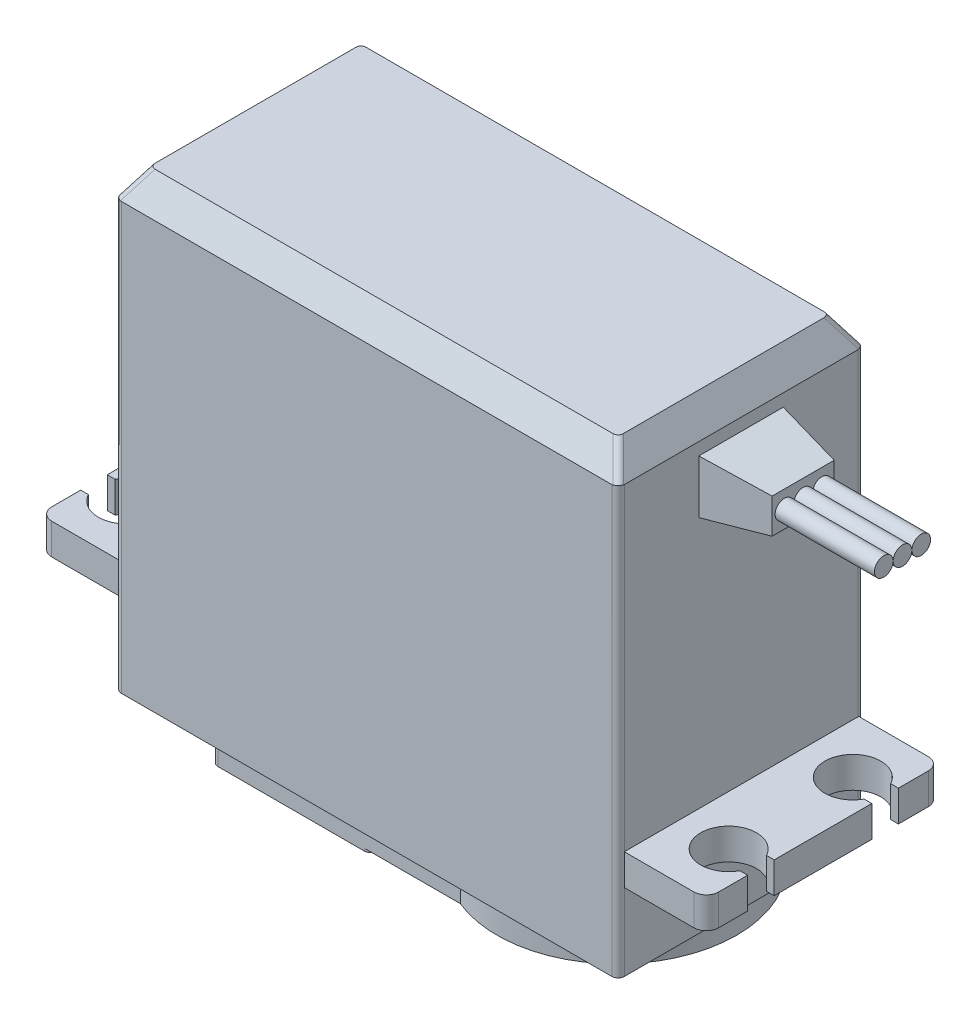
SolidWorks part; units mm, degrees
ref_plane "Front" through (0, 0, 0) normal (0, 0, 1) x (1, 0, 0)
ref_plane "Top" through (0, 0, 0) normal (0, 1, 0) x (1, 0, 0)
ref_plane "Right" through (0, 0, 0) normal (1, 0, 0) x (0, 0, -1)
sketch "Эскиз1" plane through (0, 0, 0) normal (0, 1, 0) x (1, 0, 0)
  line L1 (20.25, -9.9) -> (-20.25, -9.9)
  line L2 (20.25, -9.9) -> (20.25, 9.9)
  line L3 (20.25, 9.9) -> (-20.25, 9.9)
  line L4 (-20.25, -9.9) -> (-20.25, 9.9)
  line L5 (0, 9.9) -> (0, -9.9) construction
  line L6 (20.25, 0) -> (-20.25, 0) construction
  point P0 (0, 0)
  dimension "D1" = 19.8
  dimension "D2" = 40.5
extrude "Body" add sketch "Эскиз1" along normal blind 36.5
chamfer "Фаска1" distance 2.2 distance2 1.4 4 edges at (-20.25, 36.5, 0) (0, 36.5, -9.9) (20.25, 36.5, 0) (0, 36.5, 9.9) first distance on face at (-20.25, 18.25, 0) first distance on face at (0, 18.25, -9.9) first distance on face at (20.25, 18.25, 0) first distance on face at (0, 18.25, 9.9)
fillet "Скругление1" radius 0.5 8 edges at (-20.25, 17.15, -9.9) (-19.55, 35.4, -9.2) (19.55, 35.4, -9.2) (20.25, 17.15, -9.9) (19.55, 35.4, 9.2) (-19.55, 35.4, 9.2) (20.25, 17.15, 9.9) (-20.25, 17.15, 9.9)
ref_plane "Плоскость1" through (0, 6.2, 0) normal (0, -1, 0) x (-1, 0, 0)
sketch "Эскиз2" plane through (0, 6.2, 0) normal (0, -1, 0) x (-1, 0, 0)
  line L1 (-26.85, 9.4728) -> (26.85, 9.4728)
  line L2 (26.85, -9.4) -> (26.85, -6.0698)
  line L3 (-26.85, -9.4) -> (26.85, -9.4)
  line L4 (-26.85, -9.4) -> (-26.85, -6.0698)
  line L5 (0, 9.9) -> (0, -9.9) construction
  line L6 (27.2, 0) -> (-26.85, 0) construction
  line L7 (-24.25, 5) -> (-26.85, 5) construction
  line L8 (-26.2294, 6.0698) -> (-26.85, 6.0698)
  line L9 (-26.2294, 3.9302) -> (-26.85, 3.9302)
  line L10 (-26.85, 6.0698) -> (-26.85, 9.4728)
  line L11 (-26.2294, -3.9302) -> (-26.85, -3.9302)
  line L12 (-26.2294, -6.0698) -> (-26.85, -6.0698)
  line L13 (26.2294, -6.0698) -> (26.85, -6.0698)
  line L14 (26.2294, -3.9302) -> (26.85, -3.9302)
  line L15 (26.2294, 3.9302) -> (26.85, 3.9302)
  line L16 (26.2294, 6.0698) -> (26.85, 6.0698)
  line L17 (26.85, 6.0698) -> (26.85, 9.4728)
  line L18 (26.85, -3.9302) -> (26.85, 3.9302)
  line L19 (-26.85, -3.9302) -> (-26.85, 3.9302)
  line L20 (-20.25, -9.4) -> (-20.25, 9.4) construction
  line L21 (20.25, 9.4) -> (20.25, -9.4) construction
  arc A4 (-26.2294, 3.9302) -> (-26.2294, 6.0698) centre (-24.25, 5) ccw
  arc A5 (-26.2294, -3.9302) -> (-26.2294, -6.0698) centre (-24.25, -5) cw
  arc A6 (26.2294, -3.9302) -> (26.2294, -6.0698) centre (24.25, -5) ccw
  arc A7 (26.2294, 3.9302) -> (26.2294, 6.0698) centre (24.25, 5) cw
  point P0 (0, 0)
  point P5 (-26.85, 0)
  point P38 (-22, 5)
  point P39 (22, 5)
  dimension "D2" = 6.6
  dimension "D4" = 2.25
  dimension "D1" = 53.7
  dimension "D3" = 10
  dimension "D5" = 44
  dimension "D6" = 2.1395
  dimension "D7" = 6.6
extrude "Mount" add sketch "Эскиз2" against normal blind 2.5 contours L15 A7 L16 L17 L1 L10 L8 A4 L9 L4 L11 A5 L12 L3 L2 L13 A6 L14 L18 region at (0, 6.2, -0.039)
fillet "Скругление3" radius 1 4 edges at (-26.85, 7.45, -9.4728) (-26.85, 7.45, 9.4) (26.85, 7.45, -9.4728) (26.85, 7.45, 9.4)
sketch "Эскиз3" plane through (0, 0, 0) normal (0, 0, 1) x (1, 0, 0)
  line L0 (-26.85, 6.2) -> (-20.25, 6.2)
  line L1 (-20.25, 6.2) -> (-20.25, 5.2)
  line L2 (-20.25, 0) -> (-20.25, 6.2) construction
  line L3 (-20.25, 5.2) -> (-26.85, 6.2)
  line L4 (0, 0) -> (0, 36.5) construction
  line L5 (-18.4282, 36.5) -> (18.4282, 36.5) construction
  line L6 (20.25, 5.2) -> (26.85, 6.2)
  line L7 (20.25, 6.2) -> (20.25, 5.2)
  line L8 (26.85, 6.2) -> (20.25, 6.2)
  line L11 (-26.85, 6.2) -> (-26.85, 8.7) construction
  dimension "D1" = 1
extrude "Бобышка-Вытянуть3" add sketch "Эскиз3" along normal mid plane 1
sketch "Эскиз4" plane through (0, 0, 0) normal (0, -1, 0) x (1, 0, 0)
  line L0 (20.25, 9.4) -> (20.25, -9.4) construction
  line L1 (-13.4526, -8.92) -> (-13.4526, -4.6)
  line L2 (-13.4526, -8.92) -> (6.5681, -8.92)
  line L3 (-13.4526, 8.92) -> (6.5681, 8.92)
  line L6 (-13.4526, 4.6) -> (-13.4526, 8.92)
  arc A0 (6.5681, -8.92) -> (6.5681, 8.92) centre (10.25, 0) ccw
  arc A1 (-13.4526, 4.6) -> (-13.4526, -4.6) centre (-11.493, 0) ccw
  point P2 (20.25, 0)
  point P6 (3.35, 0)
  dimension "D1" = 19.3
  dimension "D5" = 5
  dimension "D2" = 10
  dimension "D3" = 17.84
  dimension "D4" = 9.2
extrude "Бобышка-Вытянуть4" add sketch "Эскиз4" along normal blind 2
sketch "Эскиз5" plane through (0, -2, 0) normal (0, -1, 0) x (1, 0, 0)
  line L0 (-13.4526, -8.92) -> (6.5681, -8.92) construction
  line L1 (-13.4526, 8.92) -> (-0.6526, 8.92)
  line L2 (-13.4526, 8.92) -> (-13.4526, -8.92)
  line L3 (-13.4526, -8.92) -> (-0.6526, -8.92)
  line L4 (-0.6526, 8.92) -> (-0.6526, 2)
  line L5 (-0.6526, -2) -> (-0.6526, -8.92)
  line L7 (-1.6526, -7.92) -> (-12.4526, -7.92)
  line L8 (-1.6526, -7.92) -> (-1.6526, 7.92)
  line L9 (-1.6526, 7.92) -> (-12.4526, 7.92)
  line L10 (-12.4526, -7.92) -> (-12.4526, 7.92)
  line L11 (-7.0526, 7.92) -> (-7.0526, -7.92) construction
  line L12 (-1.6526, 0) -> (-12.4526, 0) construction
  arc A0 (-0.6526, 2) -> (-0.6526, -2) centre (-0.6526, 0) cw
  point P10 (-7.0526, 0)
  dimension "D2" = 2
  dimension "D1" = 12.8
  dimension "D3" = 1
  dimension "D4" = 15.84
  dimension "D5" = 10.8
extrude "Бобышка-Вытянуть5" add sketch "Эскиз5" along normal blind 0.2
sketch "Эскиз6" plane through (0, -2, 0) normal (0, -1, 0) x (1, 0, 0)
  circle A0 centre (10.25, 0) radius 6.6
  dimension "D1" = 13.2
extrude "Бобышка-Вытянуть6" add sketch "Эскиз6" along normal blind 1.2
sketch "Эскиз7" plane through (0, -3.2, 0) normal (0, -1, 0) x (1, 0, 0)
  circle A0 centre (10.25, 0) radius 5.35
  dimension "D1" = 10.7
extrude "Бобышка-Вытянуть7" add sketch "Эскиз7" along normal blind 0.5
sketch "Эскиз8" plane through (0, -3.7, 0) normal (0, -1, 0) x (1, 0, 0)
  circle A0 centre (10.25, 0) radius 2.6
  dimension "D1" = 5.2
extrude "Shaft hole" cut sketch "Эскиз8" against normal blind 10
fillet "Скругление2" radius 0.5 10 edges at (-13.4526, -1.1, 8.92) (-0.6526, -2.1, 2) (-0.6526, -2.1, -2) (-13.4526, -1.1, -8.92) (-1.6526, -2.1, 7.92) (-1.6526, -2.1, -7.92) (-12.4526, -2.1, 7.92) (-12.4526, -2.1, -7.92)
sketch "Эскиз9" plane through (20.25, 0, 0) normal (1, 0, 0) x (0, 0, -1)
  line L0 (-8.0782, 36.5) -> (8.0782, 36.5) construction
  line L1 (-3.4, 33.3) -> (3.4, 33.3)
  line L2 (-3.4, 33.3) -> (-3.4, 29)
  line L3 (-3.4, 29) -> (3.4, 29)
  line L4 (3.4, 33.3) -> (3.4, 29)
  line L5 (0, 29) -> (0, 33.3) construction
  line L6 (-3.4, 31.15) -> (3.4, 31.15) construction
  point P0 (0, 31.15)
  dimension "D1" = 3.2
  dimension "D2" = 6.8
  dimension "D3" = 4.3
ref_plane "Плоскость2" through (25.25, 0, 0) normal (1, 0, 0) x (0, 0, -1)
sketch "Эскиз10" plane through (25.25, 0, 0) normal (1, 0, 0) x (0, 0, -1)
  line L1 (-2.5, 29.75) -> (2.5, 29.75)
  line L2 (-2.5, 29.75) -> (-2.5, 32.55)
  line L3 (-2.5, 32.55) -> (2.5, 32.55)
  line L4 (2.5, 29.75) -> (2.5, 32.55)
  line L5 (0, 32.55) -> (0, 29.75) construction
  line L6 (-2.5, 31.15) -> (2.5, 31.15) construction
  point P0 (0, 31.15)
  dimension "D1" = 2.8
  dimension "D2" = 5
loft "Rubber" add profiles "Эскиз10", "Эскиз9"
sketch "Эскиз11" plane through (25.25, 0, 0) normal (1, 0, 0) x (0, 0, -1)
  circle A0 centre (0, 31.1505) radius 0.75
  circle A1 centre (1.51, 31.15) radius 0.75
  circle A2 centre (-1.51, 31.15) radius 0.75
  dimension "D1" = 1.5
  dimension "D2" = 1.51
  dimension "D3" = 1.51
extrude "Бобышка-Вытянуть10" add sketch "Эскиз11" along normal blind 8
